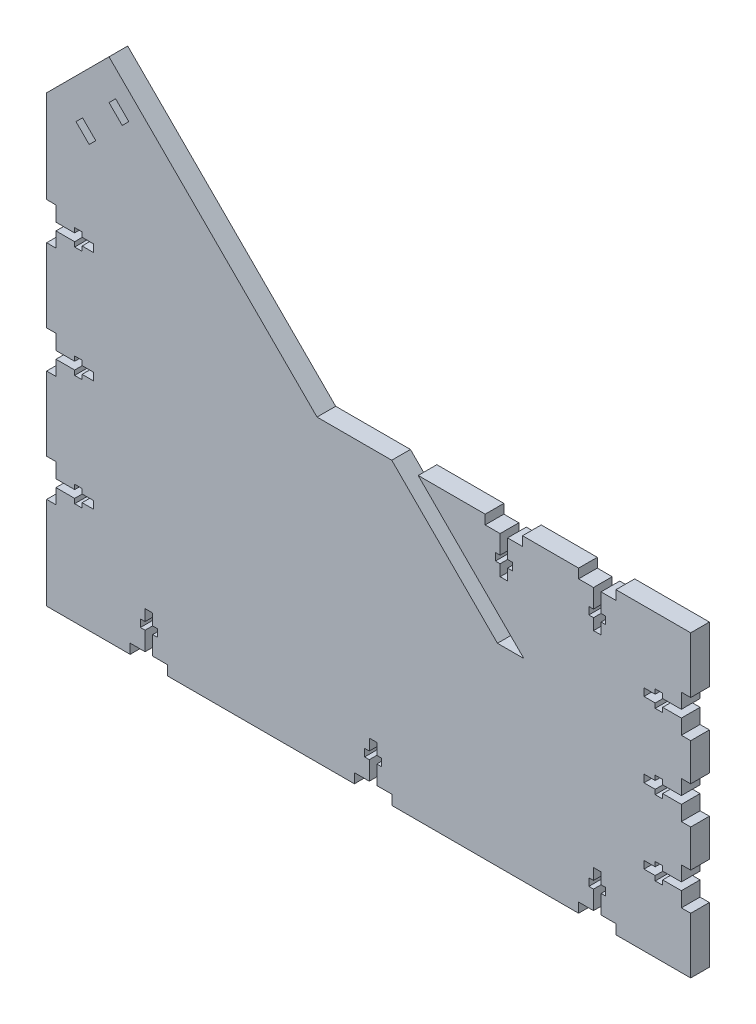
SolidWorks part; units mm, degrees
ref_plane "Front Plane" through (0, 0, 0) normal (0, 0, 1) x (1, 0, 0)
ref_plane "Top Plane" through (0, 0, 0) normal (0, 1, 0) x (1, 0, 0)
ref_plane "Right Plane" through (0, 0, 0) normal (1, 0, 0) x (0, 0, -1)
sketch "Sketch1" plane through (0, 0, 0) normal (0, 0, 1) x (1, 0, 0)
  line L0 (0, 0) -> (127, 0)
  line L1 (127, 0) -> (127, 101.6)
  line L3 (0, 101.6) -> (0, 0) construction
  line L4 (0, 101.6) -> (-70.6924, 172.2924)
  line L5 (-70.6924, 172.2924) -> (-91.8969, 151.088)
  line L6 (-91.8969, 151.088) -> (-91.8969, 0)
  line L7 (-91.8969, 0) -> (0, 0)
  line L8 (127, 101.6) -> (0, 101.6)
  dimension "D1" = 127
  dimension "D2" = 101.6
  dimension "D3" = 135
  dimension "D4" = 29.9876
  dimension "D5" = 151.088
extrude "Boss-Extrude1" add sketch "Sketch1" along normal blind 6.35
sketch "Sketch2" plane through (0, 0, 0) normal (0, 0, -1) x (-1, 0, 0)
  line L0 (0, 101.6) -> (-25.4, 101.6) construction
  line L1 (-127, 101.6) -> (0, 101.6) construction
  line L2 (-25.4, 101.6) -> (-34.3803, 101.6)
  line L3 (-25.4, 101.6) -> (-61.321, 65.679)
  line L4 (-34.3803, 101.6) -> (-70.3013, 65.679)
  line L5 (-70.3013, 65.679) -> (-61.321, 65.679)
  line L6 (-52.3408, 83.6395) -> (-43.3605, 83.6395) construction
  line L7 (-34.3803, 101.6) -> (-52.3408, 83.6395)
  line M12 (0, 101.6) -> (-127, 101.6)
  dimension "D1" = 25.4
  dimension "D2" = 8.9803
  dimension "D3" = 50.8
  dimension "D4" = 45
  dimension "D5" = 45
  dimension "D6" = 50.8
  dimension "D7" = 135
  dimension "D8" = 25.4
sketch "Sketch3" plane through (0, 0, 0) normal (0, 0, -1) x (-1, 0, 0)
  line L0 (70.6924, 172.2924) -> (61.7122, 163.3122) construction
  line L1 (0, 101.6) -> (70.6924, 172.2924) construction
  line L2 (59.4671, 161.0671) -> (63.9572, 165.5572)
  line L3 (59.4671, 161.0671) -> (63.9572, 156.577) construction
  line L5 (68.4474, 161.0671) -> (63.9572, 165.5572) construction
  line L6 (70.6924, 172.2924) -> (91.8969, 151.088) construction
  line L7 (63.9572, 156.577) -> (68.4474, 161.0671)
  line L8 (63.9572, 156.577) -> (66.2023, 154.3319)
  line L9 (68.4474, 161.0671) -> (70.6924, 158.822)
  line L10 (70.6924, 158.822) -> (66.2023, 154.3319)
  line L11 (-127, 25.4) -> (-127, 0)
  line L12 (-127, 50.8) -> (-127, 101.6) construction
  line L13 (-127, 0) -> (-127, 50.8) construction
  line L14 (-25.4, 0) -> (-12.7, 0)
  line L15 (-127, 82.55) -> (-127, 69.85)
  line L16 (0, 101.6) -> (-63.5, 101.6) construction
  line L17 (-127, 44.45) -> (-127, 57.15)
  line L18 (-127, 19.05) -> (-127, 31.75)
  line L19 (-63.5, 101.6) -> (-127, 101.6) construction
  line L20 (-101.6, 101.6) -> (-88.9, 101.6)
  line L21 (-69.85, 101.6) -> (-57.15, 101.6)
  line L22 (70.6924, 172.2924) -> (0, 101.6) construction
  line L23 (30.8561, 132.4561) -> (39.8363, 141.4363)
  line L24 (91.8969, 119.666) -> (91.8969, 106.966)
  line L25 (91.8969, 0) -> (91.8969, 75.544) construction
  line L26 (91.8969, 75.544) -> (91.8969, 151.088) construction
  line L27 (91.8969, 81.894) -> (91.8969, 69.194)
  line L28 (91.8969, 44.122) -> (91.8969, 31.422)
  line L29 (30.8561, 132.4561) -> (33.1011, 130.211)
  line L30 (-127, 82.55) -> (-123.825, 82.55)
  line L31 (-127, 82.55) -> (-127, 69.85)
  line L32 (-127, 69.85) -> (-123.825, 69.85)
  line L33 (-123.825, 82.55) -> (-123.825, 69.85) construction
  line L34 (-127, 57.15) -> (-123.825, 57.15)
  line L35 (-127, 57.15) -> (-127, 44.45)
  line L36 (-127, 44.45) -> (-123.825, 44.45)
  line L37 (-123.825, 57.15) -> (-123.825, 44.45) construction
  line L38 (-127, 31.75) -> (-123.825, 31.75)
  line L39 (-127, 31.75) -> (-127, 19.05)
  line L40 (-127, 19.05) -> (-123.825, 19.05)
  line L41 (-123.825, 31.75) -> (-123.825, 19.05) construction
  line L42 (-101.6, 101.6) -> (-88.9, 101.6)
  line L43 (-101.6, 101.6) -> (-101.6, 98.425)
  line L44 (-101.6, 98.425) -> (-88.9, 98.425) construction
  line L45 (-88.9, 101.6) -> (-88.9, 98.425)
  line L46 (-69.85, 101.6) -> (-57.15, 101.6)
  line L47 (-69.85, 101.6) -> (-69.85, 98.425)
  line L48 (-69.85, 98.425) -> (-57.15, 98.425) construction
  line L49 (-57.15, 101.6) -> (-57.15, 98.425)
  line L54 (39.8363, 141.4363) -> (42.0814, 139.1913)
  line L55 (42.0814, 139.1913) -> (33.1011, 130.211)
  line L56 (-123.825, 77.4827) -> (-123.825, 74.9173) construction
  line L57 (91.8969, 119.666) -> (88.7219, 119.666)
  line L58 (91.8969, 119.666) -> (91.8969, 106.966)
  line L59 (91.8969, 106.966) -> (88.7219, 106.966)
  line L60 (88.7219, 119.666) -> (88.7219, 106.966) construction
  line L61 (91.8969, 81.894) -> (88.7219, 81.894)
  line L62 (91.8969, 81.894) -> (91.8969, 69.194)
  line L63 (91.8969, 69.194) -> (88.7219, 69.194)
  line L64 (88.7219, 81.894) -> (88.7219, 69.194) construction
  line L65 (91.8969, 44.122) -> (88.7219, 44.122)
  line L66 (91.8969, 44.122) -> (91.8969, 31.422)
  line L67 (91.8969, 31.422) -> (88.7219, 31.422)
  line L68 (88.7219, 44.122) -> (88.7219, 31.422) construction
  line L69 (-101.6, 0) -> (-101.6, 3.302)
  line L70 (-123.825, 77.4827) -> (-117.475, 77.4827)
  line L71 (-123.825, 77.4827) -> (-123.825, 74.9173) construction
  line L72 (-123.825, 74.9173) -> (-117.475, 74.9173)
  line L73 (-111.125, 77.4827) -> (-111.125, 74.9173)
  line L74 (91.8969, 0) -> (-127, 0) construction
  line L75 (-101.6, 3.302) -> (-88.9, 3.302) construction
  line L76 (-88.9, 3.302) -> (-88.9, 0)
  line L77 (-101.6, 0) -> (-88.9, 0)
  line L78 (-25.4, 0) -> (-25.4, 3.302)
  line L79 (-25.4, 3.302) -> (-12.7, 3.302) construction
  line L80 (-12.7, 3.302) -> (-12.7, 0)
  line L81 (50.8, 0) -> (50.8, 3.302)
  line L82 (50.8, 3.302) -> (63.5, 3.302) construction
  line L83 (63.5, 3.302) -> (63.5, 0)
  line L84 (63.5, 0) -> (50.8, 0)
  line L85 (-93.9673, 3.302) -> (-96.5327, 3.302) construction
  line L86 (-96.5327, 3.302) -> (-96.5327, 9.652)
  line L87 (-96.5327, 16.002) -> (-93.9673, 16.002)
  line L88 (-93.9673, 16.002) -> (-93.9673, 12.192)
  line L89 (-17.7673, 3.302) -> (-20.3327, 3.302) construction
  line L90 (-20.3327, 3.302) -> (-20.3327, 9.652)
  line L91 (-20.3327, 16.002) -> (-17.7673, 16.002)
  line L92 (-17.7673, 16.002) -> (-17.7673, 12.192)
  line L93 (58.4327, 3.302) -> (55.8673, 3.302) construction
  line L94 (55.8673, 3.302) -> (55.8673, 9.652)
  line L95 (55.8673, 16.002) -> (58.4327, 16.002)
  line L96 (58.4327, 16.002) -> (58.4327, 12.192)
  line L97 (-123.825, 24.1173) -> (-123.825, 26.6827) construction
  line L98 (-123.825, 26.6827) -> (-117.475, 26.6827)
  line L99 (-111.125, 26.6827) -> (-111.125, 24.1173)
  line L100 (-111.125, 24.1173) -> (-114.935, 24.1173)
  line L101 (-123.825, 49.5173) -> (-123.825, 52.0827) construction
  line L102 (-123.825, 52.0827) -> (-117.475, 52.0827)
  line L103 (-111.125, 52.0827) -> (-111.125, 49.5173)
  line L104 (-111.125, 49.5173) -> (-114.935, 49.5173)
  line L105 (-93.9673, 98.425) -> (-96.5327, 98.425) construction
  line L106 (-96.5327, 98.425) -> (-96.5327, 92.075)
  line L107 (-96.5327, 85.725) -> (-93.9673, 85.725)
  line L108 (-93.9673, 85.725) -> (-93.9673, 89.535)
  line L109 (-62.23, 98.425) -> (-64.77, 98.425) construction
  line L110 (-64.77, 98.425) -> (-64.77, 92.075)
  line L111 (-64.77, 85.725) -> (-62.23, 85.725)
  line L112 (-62.23, 85.725) -> (-62.23, 89.535)
  line L113 (88.7219, 112.0333) -> (88.7219, 114.5987) construction
  line L114 (88.7219, 114.5987) -> (82.3719, 114.5987)
  line L115 (76.0219, 114.5987) -> (76.0219, 112.0333)
  line L116 (76.0219, 112.0333) -> (79.8319, 112.0333)
  line L117 (88.7219, 74.2613) -> (88.7219, 76.8267) construction
  line L118 (88.7219, 76.8267) -> (82.3719, 76.8267)
  line L119 (76.0219, 76.8267) -> (76.0219, 74.2613)
  line L120 (76.0219, 74.2613) -> (79.8319, 74.2613)
  line L121 (88.7219, 36.4893) -> (88.7219, 39.0547) construction
  line L122 (88.7219, 39.0547) -> (82.3719, 39.0547)
  line L123 (76.0219, 39.0547) -> (76.0219, 36.4893)
  line L124 (76.0219, 36.4893) -> (79.8319, 36.4893)
  line L125 (-123.825, 44.45) -> (-123.825, 49.5173)
  line L126 (-123.825, 52.0827) -> (-123.825, 57.15) construction
  line L127 (-123.825, 82.55) -> (-123.825, 77.4827)
  line L128 (-123.825, 74.9173) -> (-123.825, 69.85)
  line L129 (-123.825, 57.15) -> (-123.825, 52.0827)
  line L130 (-123.825, 52.0827) -> (-123.825, 57.15)
  line L131 (-123.825, 26.6827) -> (-123.825, 31.75)
  line L132 (-123.825, 19.05) -> (-123.825, 24.1173)
  line L133 (-101.6, 3.302) -> (-96.5327, 3.302)
  line L135 (-101.6, 98.425) -> (-96.5327, 98.425)
  line L136 (-93.9673, 98.425) -> (-88.9, 98.425)
  line L137 (-64.77, 98.425) -> (-69.85, 98.425)
  line L138 (-62.23, 98.425) -> (-57.15, 98.425)
  line L139 (-93.9673, 3.302) -> (-88.9, 3.302)
  line L140 (-25.4, 3.302) -> (-20.3327, 3.302)
  line L141 (-17.7673, 3.302) -> (-12.7, 3.302)
  line L142 (50.8, 3.302) -> (55.8673, 3.302)
  line L143 (58.4327, 3.302) -> (63.5, 3.302)
  line L144 (88.7219, 39.0547) -> (88.7219, 44.122)
  line L145 (88.7219, 31.422) -> (88.7219, 36.4893)
  line L146 (88.7219, 69.194) -> (88.7219, 74.2613)
  line L147 (88.7219, 76.8267) -> (88.7219, 81.894)
  line L148 (88.7219, 106.966) -> (88.7219, 112.0333)
  line L149 (88.7219, 114.5987) -> (88.7219, 119.666)
  line L150 (82.3719, 39.0547) -> (82.3719, 40.6422)
  line L151 (82.3719, 40.6422) -> (79.8319, 40.6422)
  line L152 (79.8319, 40.6422) -> (79.8319, 39.0547)
  line L153 (79.8319, 34.9018) -> (82.3719, 34.9018)
  line L154 (82.3719, 34.9018) -> (82.3719, 36.4893)
  line L156 (82.3719, 76.8267) -> (82.3719, 78.4142)
  line L157 (82.3719, 78.4142) -> (79.8319, 78.4142)
  line L158 (79.8319, 78.4142) -> (79.8319, 76.8267)
  line L159 (79.8319, 72.6738) -> (82.3719, 72.6738)
  line L160 (82.3719, 72.6738) -> (82.3719, 74.2613)
  line L162 (82.3719, 114.5987) -> (82.3719, 116.1862)
  line L163 (82.3719, 116.1862) -> (79.8319, 116.1862)
  line L164 (79.8319, 116.1862) -> (79.8319, 114.5987)
  line L165 (79.8319, 110.4458) -> (82.3719, 110.4458)
  line L166 (82.3719, 110.4458) -> (82.3719, 112.0333)
  line L168 (58.4327, 9.652) -> (60.0202, 9.652)
  line L169 (60.0202, 9.652) -> (60.0202, 12.192)
  line L170 (60.0202, 12.192) -> (58.4327, 12.192)
  line L171 (54.2798, 12.192) -> (54.2798, 9.652)
  line L172 (54.2798, 9.652) -> (55.8673, 9.652)
  line L174 (-17.7673, 9.652) -> (-16.1798, 9.652)
  line L175 (-16.1798, 9.652) -> (-16.1798, 12.192)
  line L176 (-16.1798, 12.192) -> (-17.7673, 12.192)
  line L177 (-21.9202, 12.192) -> (-21.9202, 9.652)
  line L178 (-21.9202, 9.652) -> (-20.3327, 9.652)
  line L180 (-93.9673, 9.652) -> (-92.3798, 9.652)
  line L181 (-92.3798, 9.652) -> (-92.3798, 12.192)
  line L182 (-92.3798, 12.192) -> (-93.9673, 12.192)
  line L183 (-98.1202, 12.192) -> (-98.1202, 9.652)
  line L184 (-98.1202, 9.652) -> (-96.5327, 9.652)
  line L186 (-117.475, 26.6827) -> (-117.475, 28.2702)
  line L187 (-117.475, 28.2702) -> (-114.935, 28.2702)
  line L188 (-114.935, 28.2702) -> (-114.935, 26.6827)
  line L189 (-114.935, 24.1173) -> (-114.935, 22.5298)
  line L190 (-114.935, 22.5298) -> (-117.475, 22.5298)
  line L191 (-117.475, 22.5298) -> (-117.475, 24.1173)
  line L193 (-117.475, 52.0827) -> (-117.475, 53.6702)
  line L194 (-117.475, 53.6702) -> (-114.935, 53.6702)
  line L195 (-114.935, 53.6702) -> (-114.935, 52.0827)
  line L196 (-114.935, 49.5173) -> (-114.935, 47.9298)
  line L197 (-114.935, 47.9298) -> (-117.475, 47.9298)
  line L198 (-117.475, 47.9298) -> (-117.475, 49.5173)
  line L200 (-117.475, 77.4827) -> (-117.475, 79.0702)
  line L201 (-117.475, 79.0702) -> (-114.935, 79.0702)
  line L202 (-114.935, 79.0702) -> (-114.935, 77.4827)
  line L203 (-114.935, 73.3298) -> (-117.475, 73.3298)
  line L204 (-117.475, 73.3298) -> (-117.475, 74.9173)
  line L206 (-96.5327, 92.075) -> (-98.1202, 92.075)
  line L207 (-98.1202, 92.075) -> (-98.1202, 89.535)
  line L208 (-98.1202, 89.535) -> (-96.5327, 89.535)
  line L209 (-92.3798, 89.535) -> (-92.3798, 92.075)
  line L210 (-92.3798, 92.075) -> (-93.9673, 92.075)
  line L212 (-64.77, 92.075) -> (-66.3575, 92.075)
  line L213 (-66.3575, 92.075) -> (-66.3575, 89.535)
  line L214 (-66.3575, 89.535) -> (-64.77, 89.535)
  line L215 (-60.6425, 89.535) -> (-60.6425, 92.075)
  line L216 (-60.6425, 92.075) -> (-62.23, 92.075)
  line L218 (-114.935, 26.6827) -> (-111.125, 26.6827)
  line L219 (-117.475, 24.1173) -> (-123.825, 24.1173)
  line L220 (-96.5327, 12.192) -> (-98.1202, 12.192)
  line L221 (-93.9673, 9.652) -> (-93.9673, 3.302)
  line L222 (-96.5327, 12.192) -> (-96.5327, 16.002)
  line L223 (-20.3327, 12.192) -> (-21.9202, 12.192)
  line L224 (-20.3327, 12.192) -> (-20.3327, 16.002)
  line L225 (-17.7673, 9.652) -> (-17.7673, 3.302)
  line L226 (58.4327, 9.652) -> (58.4327, 3.302)
  line L227 (55.8673, 12.192) -> (55.8673, 16.002)
  line L228 (55.8673, 12.192) -> (54.2798, 12.192)
  line L229 (79.8319, 36.4893) -> (79.8319, 34.9018)
  line L230 (79.8319, 39.0547) -> (76.0219, 39.0547)
  line L231 (82.3719, 36.4893) -> (88.7219, 36.4893)
  line L232 (79.8319, 76.8267) -> (76.0219, 76.8267)
  line L233 (82.3719, 74.2613) -> (88.7219, 74.2613)
  line L234 (79.8319, 74.2613) -> (79.8319, 72.6738)
  line L235 (79.8319, 114.5987) -> (76.0219, 114.5987)
  line L236 (82.3719, 112.0333) -> (88.7219, 112.0333)
  line L237 (79.8319, 112.0333) -> (79.8319, 110.4458)
  line L238 (-62.23, 89.535) -> (-60.6425, 89.535)
  line L239 (-62.23, 92.075) -> (-62.23, 98.425)
  line L240 (-64.77, 89.535) -> (-64.77, 85.725)
  line L241 (-93.9673, 92.075) -> (-93.9673, 98.425)
  line L242 (-96.5327, 89.535) -> (-96.5327, 85.725)
  line L243 (-93.9673, 89.535) -> (-92.3798, 89.535)
  line L244 (-114.935, 74.9173) -> (-114.935, 73.3298)
  line L245 (-114.935, 77.4827) -> (-111.125, 77.4827)
  line L246 (-114.935, 74.9173) -> (-111.125, 74.9173)
  line L247 (-114.935, 52.0827) -> (-111.125, 52.0827)
  line L248 (-117.475, 49.5173) -> (-123.825, 49.5173)
  point P8 (61.7122, 163.3122)
  point P27 (-127, 76.2)
  point P30 (-127, 50.8)
  point P33 (-127, 25.4)
  point P34 (-95.25, 101.6)
  point P36 (-95.25, 101.6)
  point P39 (-63.5, 85.725)
  point P41 (-31.75, 101.6)
  point P42 (-63.5, 101.6)
  point P45 (35.3462, 136.9462)
  point P53 (91.8969, 113.316)
  point P56 (91.8969, 75.544)
  point P59 (91.8969, 37.772)
  point P70 (-95.25, 3.302)
  point P82 (-123.825, 76.2)
  point P102 (-19.05, 3.302)
  point P107 (57.15, 3.302)
  point P112 (-123.825, 25.4)
  point P117 (-123.825, 50.8)
  point P122 (-95.25, 98.425)
  point P127 (-63.5, 98.425)
  point P132 (88.7219, 113.316)
  point P137 (88.7219, 75.544)
  point P142 (88.7219, 37.772)
  line M40 (-127, 0) -> (91.8969, 0)
  line M41 (91.8969, 0) -> (91.8969, 151.088)
  line M44 (0, 101.6) -> (-127, 101.6)
  line M45 (-127, 101.6) -> (-127, 0)
  dimension "D1" = 12.7
  dimension "D2" = 9.525
  dimension "D3" = 6.35
  dimension "D4" = 6.35
  dimension "D5" = 6.35
  dimension "D6" = 3.175
  dimension "D7" = 3.175
  dimension "D8" = 12.7
  dimension "D9" = 12.7
  dimension "D10" = 12.7
  dimension "D11" = 25.4
  dimension "D12" = 12.7
  dimension "D13" = 12.7
  dimension "D14" = 12.7
  dimension "D15" = 31.75
  dimension "D16" = 12.7
  dimension "D17" = 75.544
  dimension "D18" = 12.7
  dimension "D19" = 12.7
  dimension "D20" = 12.7
  dimension "D21" = 3.175
  dimension "D22" = 3.175
  dimension "D23" = 3.175
  dimension "D24" = 3.175
  dimension "D25" = 3.175
  dimension "D26" = 3.302
  dimension "D27" = 3.175
  dimension "D28" = 3.175
  dimension "D29" = 12.7
  dimension "D30" = 3.175
  dimension "D31" = 3.175
  dimension "D32" = 3.175
  dimension "D33" = 2.5654
  dimension "D34" = 12.7
  dimension "D35" = 25.4
  dimension "D36" = 63.5
  dimension "D37" = 63.5
  dimension "D38" = 3.302
  dimension "D39" = 12.7
  dimension "D40" = 12.7
  dimension "D41" = 3.302
  dimension "D42" = 2.5654
  dimension "D43" = 12.7
  dimension "D44" = 12.7
  dimension "D45" = 2.5654
  dimension "D46" = 12.7
  dimension "D47" = 2.5654
  dimension "D48" = 12.7
  dimension "D49" = 2.5654
  dimension "D50" = 12.7
  dimension "D51" = 1.27
  dimension "D52" = 12.7
  dimension "D53" = 2.5654
  dimension "D54" = 2.5654
  dimension "D55" = 12.7
  dimension "D56" = 2.5654
  dimension "D57" = 12.7
  dimension "D58" = 12.7
  dimension "D59" = 2.5654
  dimension "D60" = 12.7
  dimension "D61" = 2.5654
  dimension "D62" = 1.5875
  dimension "D63" = 1.5875
  dimension "D64" = 2.54
  dimension "D65" = 1.5875
  dimension "D66" = 1.5875
  dimension "D67" = 2.54
  dimension "D68" = 2.54
  dimension "D69" = 1.5875
  dimension "D70" = 2.54
  dimension "D71" = 1.5875
  dimension "D72" = 5.7404
  dimension "D73" = 1.5875
  dimension "D74" = 1.5875
  dimension "D75" = 2.54
  dimension "D76" = 1.5875
  dimension "D77" = 1.5875
  dimension "D78" = 2.54
  dimension "D79" = 90
  dimension "D80" = 1.5875
  dimension "D81" = 1.5875
  dimension "D82" = 2.54
  dimension "D83" = 270
  dimension "D84" = 1.5875
  dimension "D85" = 1.5875
  dimension "D86" = 2.54
  dimension "D87" = 1.5875
  dimension "D88" = 1.5875
  dimension "D89" = 2.54
  dimension "D90" = 270
  dimension "D91" = 2.54
  dimension "D92" = 1.5875
  dimension "D93" = 1.5875
  dimension "D94" = 90
  dimension "D95" = 2.54
  dimension "D96" = 1.5875
  dimension "D97" = 1.5875
  dimension "D98" = 1.5875
  dimension "D99" = 1.5875
  dimension "D100" = 2.54
  dimension "D102" = 270
extrude "Cut-Extrude2" cut sketch "Sketch2" against normal blind 127 and the other way blind 2.54 contours L4 L5 L3 M12 region at (47.8506, 83.6395, 0)
extrude "Cut-Extrude4" cut sketch "Sketch3" against normal blind 127 and the other way blind 127 contours L108 L136 L45 L43 L135 L106 L107 M44 | L112 L138 L49 L47 L137 L110 L111 M44 | L128 L72 L73 L70 L127 L30 L32 M45 | L129 L34 L36 L125 L104 L103 L102 M45 | L40 L132 L100 L99 L98 L131 L38 M45 | L139 L88 L87 L86 L133 L69 L76 M40 | L141 L92 L91 L90 L140 L78 L80 M40 | L143 L96 L95 L94 L142 L81 L83 M40 | L145 L67 L65 L144 L122 L123 L124 M41 | L147 L118 L119 L120 L146 L63 L61 M41 | L149 L114 L115 L116 L148 L59 L57 M41 | L10 L9 L7 L8 region at (-67.3248, 157.6995, 0) region at (121.3014, 25.4, 0) region at (63.5, 95.9167, 0) region at (95.25, 95.9014, 0) region at (121.3014, 76.2, 0) region at (121.3014, 50.8, 0) region at (-86.1983, 113.316, 0) region at (-86.1983, 75.544, 0) region at (-86.1983, 37.772, 0) region at (-57.15, 5.713, 0) region at (19.05, 5.713, 0) region at (95.25, 5.713, 0)
sketch "Sketch4" plane through (0, 0, 0) normal (0, 0, 1) x (1, 0, 0)
  line L0 (-81.9177, 147.5967) -> (-79.6727, 149.8418)
  line L1 (-81.9177, 147.5967) -> (-77.4276, 143.1066)
  line L2 (-77.4276, 143.1066) -> (-75.1826, 145.3517)
  line L3 (-75.1826, 145.3517) -> (-79.6727, 149.8418)
  line L5 (-70.6924, 158.822) -> (-66.2023, 154.3319) construction
  line L6 (-70.6924, 172.2924) -> (-91.8969, 151.088) construction
  dimension "D1" = 3.175
  dimension "D2" = 6.35
  dimension "D3" = 12.7
  dimension "D4" = 9.525
extrude "Cut-Extrude5" cut sketch "Sketch4" against normal blind 127 and the other way blind 127 contours L0 L3 L2 L1
